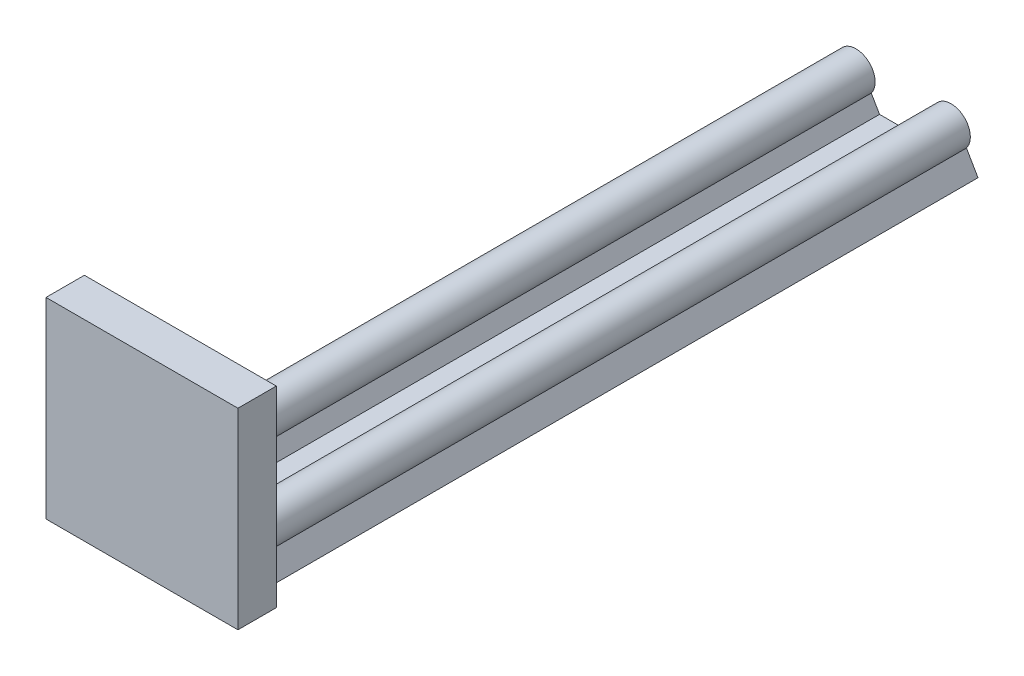
SolidWorks part; units mm, degrees
ref_plane "Front Plane" through (0, 0, 0) normal (0, 0, 1) x (1, 0, 0)
ref_plane "Top Plane" through (0, 0, 0) normal (0, 1, 0) x (1, 0, 0)
ref_plane "Right Plane" through (0, 0, 0) normal (1, 0, 0) x (0, 0, -1)
sketch "Sketch1" plane through (0, 0, 0) normal (0, 0, 1) x (1, 0, 0)
  line L0 (-4, -3) -> (4, -3) construction
  line L1 (-4, -3) -> (-7, -8.1962)
  line L2 (4, -3) -> (7, -8.1962)
  line L3 (-7, -8.1962) -> (7, -8.1962)
  line L4 (28.8, -3) -> (31.8, -8.1962)
  line L5 (17.8, -8.1962) -> (31.8, -8.1962)
  line L6 (20.8, -3) -> (17.8, -8.1962)
  circle A0 centre (0, 0) radius 5
  arc A1 (-4, -3) -> (4, -3) centre (0, 0) cw
  arc A2 (20.8, -3) -> (28.8, -3) centre (24.8, 0) cw
  dimension "D1" = 3
  dimension "D2" = 2
  dimension "D3" = 8
extrude "Boss-Extrude1" add sketch "Sketch1" along normal blind 220 contours A0 L0 | L0 A0 | A0 L1 L3 L2 | L4 L5 L6 A2 region at (0, 0.6334, 0) region at (0, -6.3253, 0) region at (0, -3.8155, 0)
sketch "Sketch3" plane through (0, 0, 220) normal (0, 0, 1) x (1, 0, 0)
  line L0 (7, -8.1962) -> (17.8, -8.1962)
  line L1 (6.15, -6.7239) -> (18.65, -6.7239)
  line L2 (4, -3) -> (7, -8.1962) construction
  line L3 (20.8, -3) -> (17.8, -8.1962) construction
  line L4 (18.65, -6.7239) -> (18.65, -8.1962)
  line L5 (17.8, -8.1962) -> (31.8, -8.1962) construction
  line L6 (18.65, -8.1962) -> (17.8, -8.1962)
  line L7 (6.15, -6.7239) -> (6.15, -8.1962)
  line L8 (-7, -8.1962) -> (7, -8.1962) construction
  line L9 (6.15, -8.1962) -> (7, -8.1962)
  dimension "D1" = 12.5
sketch "Sketch4" plane through (0, -8.1962, 0) normal (0, -1, 0) x (1, 0, 0)
  line L0 (24.8, 220) -> (24.8, 0) construction
  line L1 (17.8, 220) -> (31.8, 220) construction
  line L2 (17.8, 0) -> (31.8, 0) construction
  line L3 (0, 0) -> (0, 220) construction
  line L4 (-7, 220) -> (7, 220) construction
  circle A0 centre (0, 197.5) radius 3.2
  circle A1 centre (24.8, 197.5) radius 3.2
  circle A2 centre (24.8, 172.6) radius 3.2
  circle A3 centre (24.8, 147.7) radius 3.2
  circle A4 centre (24.8, 122.8) radius 3.2
  circle A5 centre (24.8, 97.9) radius 3.2
  circle A6 centre (24.8, 73) radius 3.2
  circle A7 centre (24.8, 48.1) radius 3.2
  circle A8 centre (24.8, 23.2) radius 3.2
  circle A9 centre (0, 172.6) radius 3.2
  circle A10 centre (0, 147.7) radius 3.2
  circle A11 centre (0, 122.8) radius 3.2
  circle A12 centre (0, 97.9) radius 3.2
  circle A13 centre (0, 73) radius 3.2
  circle A14 centre (0, 48.1) radius 3.2
  circle A15 centre (0, 23.2) radius 3.2
  dimension "D1" = 2
  dimension "D3" = 23.2
  dimension "D2" = 8
extrude "Boss-Extrude3" [suppressed] add sketch "Sketch4" along normal blind 6
extrude "Boss-Extrude4" add sketch "Sketch3" against normal blind 220
sketch "Sketch5" plane through (0, 0, 0) normal (0, 0, -1) x (-1, 0, 0)
  circle A0 centre (0, 0) radius 1.37
  circle A1 centre (-24.8, 0) radius 1.37
  dimension "D1" = 2
extrude "Cut-Extrude1" cut sketch "Sketch5" against normal blind 7
sketch "Sketch6" plane through (0, 0, 220) normal (0, 0, 1) x (1, 0, 0)
  circle A0 centre (0, 0) radius 1.37
  circle A1 centre (24.8, 0) radius 1.37
  dimension "D1" = 2
extrude "Cut-Extrude2" cut sketch "Sketch6" against normal blind 7
sketch "Sketch7" [suppressed] plane through (0, -14.1962, 0) normal (0, -1, 0) x (1, 0, 0)
  circle A0 centre (0, 172) radius 3.2
  circle A1 centre (24.8, 172) radius 3.2
  circle A2 centre (24.8, 147.2) radius 3.2
  circle A3 centre (24.8, 122.4) radius 3.2
  circle A4 centre (24.8, 97.6) radius 3.2
  circle A5 centre (24.8, 72.8) radius 3.2
  circle A6 centre (24.8, 48) radius 3.2
  circle A7 centre (0, 147.2) radius 3.2
  circle A8 centre (0, 122.4) radius 3.2
  circle A9 centre (0, 97.6) radius 3.2
  circle A10 centre (0, 72.8) radius 3.2
  circle A11 centre (0, 48) radius 3.2
  dimension "D1" = 2
  dimension "D2" = 6
extrude "Cut-Extrude3" [suppressed] cut sketch "Sketch7" against normal blind 6
sketch "Sketch9" plane through (0, 0, 0) normal (0, 0, -1) x (-1, 0, 0)
  line L6 (-28.8, -3) -> (-31.8, -8.1962)
  line L7 (-31.8, -8.1962) -> (7, -8.1962)
  line L8 (7, -8.1962) -> (4, -3)
  line L9 (-4, -3) -> (-6.15, -6.7239)
  line L10 (-6.15, -6.7239) -> (-18.65, -6.7239)
  line L11 (-18.65, -6.7239) -> (-20.8, -3)
  line L12 (-28.8, -3) -> (-31.8, -8.1962)
  line L13 (-31.8, -8.1962) -> (7, -8.1962)
  line L14 (7, -8.1962) -> (4, -3)
  line L15 (-4, -3) -> (-6.15, -6.7239)
  line L16 (-6.15, -6.7239) -> (-18.65, -6.7239)
  line L17 (-18.65, -6.7239) -> (-20.8, -3)
  arc A2 (4, -3) -> (-4, -3) centre (0, 0) ccw
  arc A3 (-20.8, -3) -> (-28.8, -3) centre (-24.8, 0) ccw
  arc A4 (4, -3) -> (-4, -3) centre (0, 0) ccw
  arc A5 (-20.8, -3) -> (-28.8, -3) centre (-24.8, 0) ccw
  dimension "D1" = 0
extrude "Cut-Extrude4" cut sketch "Sketch9" against normal blind 10.8
sketch "Sketch10" plane through (0, 0, 220) normal (0, 0, 1) x (1, 0, 0)
  line L6 (20.8, -3) -> (18.65, -6.7239)
  line L7 (18.65, -6.7239) -> (6.15, -6.7239)
  line L8 (6.15, -6.7239) -> (4, -3)
  line L9 (-4, -3) -> (-7, -8.1962)
  line L10 (-7, -8.1962) -> (31.8, -8.1962)
  line L11 (31.8, -8.1962) -> (28.8, -3)
  line L12 (20.8, -3) -> (18.65, -6.7239)
  line L13 (18.65, -6.7239) -> (6.15, -6.7239)
  line L14 (6.15, -6.7239) -> (4, -3)
  line L15 (-4, -3) -> (-7, -8.1962)
  line L16 (-7, -8.1962) -> (31.8, -8.1962)
  line L17 (31.8, -8.1962) -> (28.8, -3)
  arc A2 (4, -3) -> (-4, -3) centre (0, 0) ccw
  arc A3 (28.8, -3) -> (20.8, -3) centre (24.8, 0) ccw
  arc A4 (4, -3) -> (-4, -3) centre (0, 0) ccw
  arc A5 (28.8, -3) -> (20.8, -3) centre (24.8, 0) ccw
  dimension "D1" = 0
extrude "Cut-Extrude5" cut sketch "Sketch10" against normal blind 10.8
sketch "Sketch11" plane through (0, 0, 209.2) normal (0, 0, 1) x (1, 0, 0)
  circle A0 centre (0, 0) radius 2
  circle A1 centre (24.8, 0) radius 2
  dimension "D1" = 2
extrude "Cut-Extrude6" cut sketch "Sketch11" against normal blind 7
sketch "Sketch12" plane through (0, 0, 10.8) normal (0, 0, -1) x (-1, 0, 0)
  circle A0 centre (0, 0) radius 1.5
  circle A1 centre (-24.8, 0) radius 1.5
  dimension "D1" = 2
  dimension "D2" = 3
extrude "Cut-Extrude7" cut sketch "Sketch12" against normal blind 7
sketch "Sketch13" plane through (0, 0, 209.2) normal (0, 0, 1) x (1, 0, 0)
  line L0 (-7, -8.1962) -> (31.8, -8.1962) construction
  line L1 (-12.6, 41.8038) -> (37.4, 41.8038)
  line L2 (-12.6, 41.8038) -> (-12.6, -8.1962)
  line L3 (-12.6, -8.1962) -> (37.4, -8.1962)
  line L4 (37.4, 41.8038) -> (37.4, -8.1962)
  point P8 (12.4, -8.1962)
  point P9 (12.4, -8.1962)
  dimension "D1" = 50
  dimension "D2" = 50
extrude "Boss-Extrude5" add sketch "Sketch13" against normal blind 10
sketch "Sketch14" plane through (0, 0, 199.2) normal (0, 0, -1) x (-1, 0, 0)
  line L0 (-12.4, -8.1962) -> (-12.4, 41.8038) construction
  line L1 (-31.8, -8.1962) -> (7, -8.1962) construction
  line L2 (-37.4, 41.8038) -> (12.6, 41.8038) construction
  circle A0 centre (-12.4, 22.3038) radius 5
  dimension "D2" = 10
  dimension "D1" = 30.5
extrude "Cut-Extrude8" cut sketch "Sketch14" against normal blind 5
extrude "Cut-Extrude9" cut sketch "Sketch4<2>" against normal blind 5 contours A1 | A8 | A15 | A0 region at (24.8, -8.1962, 197.5)
sketch "Sketch4<2>" plane through (0, -8.1962, 0) normal (0, -1, 0) x (1, 0, 0) same geometry as "Sketch4"
